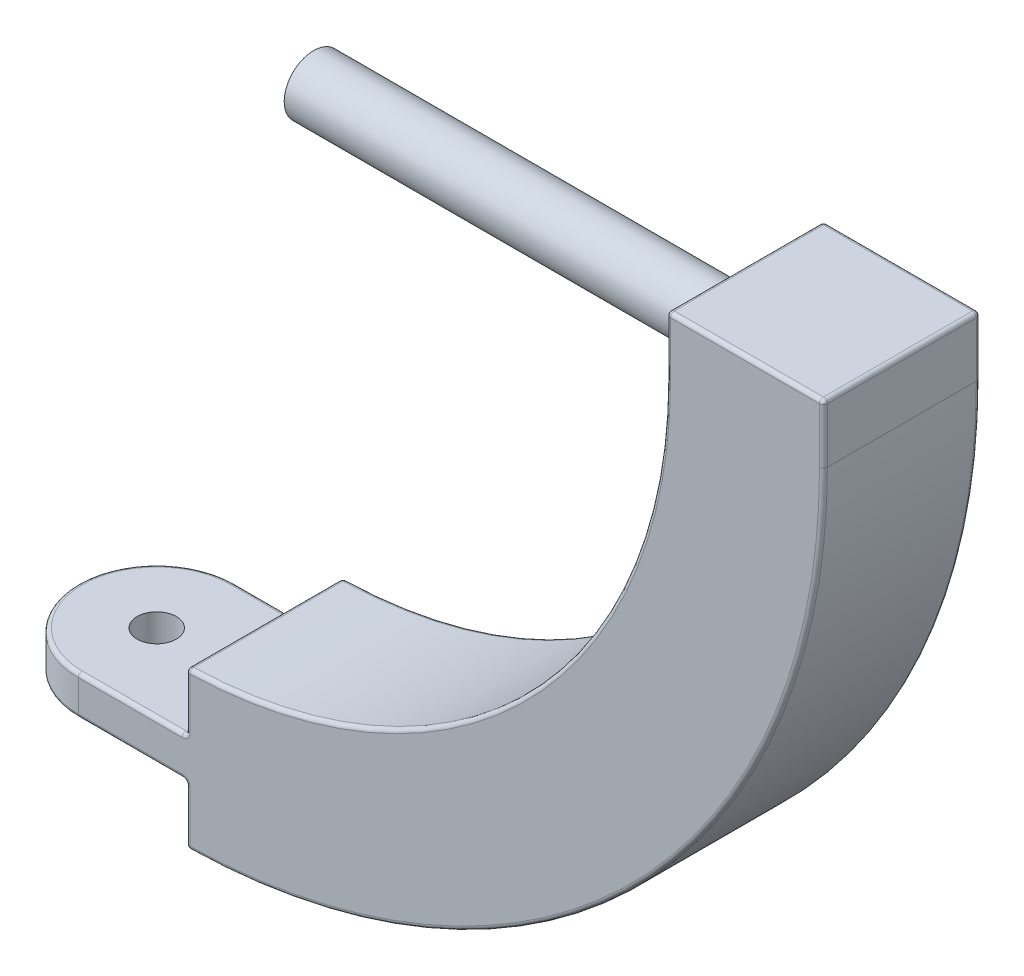
SolidWorks part; units mm, degrees
material "Thornel Mat VMA"
ref_plane "Front Plane" through (0, 0, 0) normal (0, 0, 1) x (1, 0, 0)
ref_plane "Top Plane" through (0, 0, 0) normal (0, 1, 0) x (1, 0, 0)
ref_plane "Right Plane" through (0, 0, 0) normal (1, 0, 0) x (0, 0, -1)
ref_plane "Plane1" through (0, 0, 150) normal (0, 0, 1) x (1, 0, 0)
sketch "Sketch1" plane through (0, 0, 150) normal (0, 0, 1) x (1, 0, 0)
  line L0 (200, 200) -> (200, 35) construction
  line L1 (325, 200) -> (365, 200)
  line L2 (202.5, 75.025) -> (202.5, 60.025)
  line L3 (202.5, 60.025) -> (155, 60.025)
  line L4 (155, 60.025) -> (155, 50.0189)
  line L5 (155, 50.0189) -> (202.5, 50.0189)
  line L6 (202.5, 50.0189) -> (202.5, 35.0189)
  arc A2 (202.5, 75.025) -> (325, 200) centre (200, 200) ccw
  arc A3 (202.5, 35.0189) -> (365, 200) centre (200, 200) ccw
  dimension "D1" = 200
  dimension "D3" = 40
  dimension "D5" = 2.5
  dimension "D2" = 200
  dimension "D6" = 2.5
  dimension "D7" = 47.5
  dimension "D8" = 15
  dimension "D9" = 15
extrude "Boss-Extrude1" add sketch "Sketch1" against normal blind 40
fillet "Fillet1" radius 20 2 edges at (155, 55.022, 110) (155, 55.022, 150)
sketch "Sketch3" plane through (0, 60.025, 0) normal (0, 1, 0) x (-1, 0, 0)
  circle A0 centre (-175, 130) radius 5
extrude "Cut-Extrude1" cut sketch "Sketch3" against normal blind 29
sketch "Sketch4" plane through (0, 200, 0) normal (0, 1, 0) x (-1, 0, 0)
  line L1 (-365, 150) -> (-325, 150)
  line L2 (-365, 150) -> (-365, 110)
  line L3 (-365, 110) -> (-325, 110)
  line L4 (-325, 150) -> (-325, 110)
  line L5 (-365, 150) -> (-325, 110) construction
  line L6 (-365, 110) -> (-325, 150) construction
  point P0 (-345, 130)
extrude "Boss-Extrude2" add sketch "Sketch4" along normal blind 15
sketch "Sketch5" plane through (325, 0, 0) normal (-1, 0, 0) x (0, -1, 0)
  line L0 (-200, 110) -> (-200, 150) construction
  circle A0 centre (-200, 130) radius 7.5
extrude "Boss-Extrude3" add sketch "Sketch5" along normal blind 110
fillet "Fillet2" radius 1 28 edges at (325, 207.5, 110) (365, 207.5, 110) (188.75, 60.025, 110) (160.8579, 60.025, 115.8579) (160.8579, 60.025, 144.1421) (188.75, 50.0189, 110) (160.8579, 50.0189, 115.8579) (160.8579, 50.0189, 144.1421) (365, 207.5, 150) (325, 207.5, 150) (202.5, 50.0189, 130) (202.5, 60.025, 130) (202.5, 67.525, 150) (202.5, 67.525, 110) (202.5, 75.025, 130) (365, 215, 130) (345, 215, 110) (325, 215, 130) (345, 215, 150) (202.5, 42.5189, 110) (289.2679, 112.5, 110) (317.5532, 84.2146, 110) (202.5, 35.0189, 130) (202.5, 42.5189, 150) (188.75, 60.025, 150) (188.75, 50.0189, 150) (317.5532, 84.2146, 150) (289.2679, 112.5, 150)
